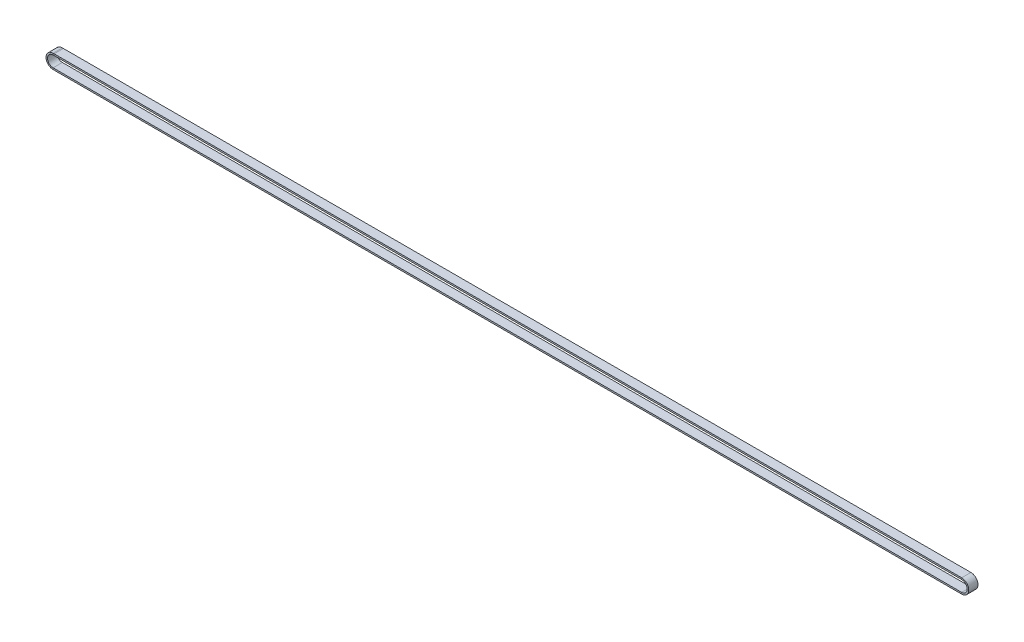
SolidWorks part; units mm, degrees
ref_plane "Front Plane" through (0, 0, 0) normal (0, 0, 1) x (1, 0, 0)
ref_plane "Top Plane" through (0, 0, 0) normal (0, 1, 0) x (1, 0, 0)
ref_plane "Right Plane" through (0, 0, 0) normal (1, 0, 0) x (0, 0, -1)
sketch "Sketch2" plane through (0, 0, -93.7334) normal (0, 0, 1) x (1, 0, 0)
  line L0 (0, 0) -> (1, 0) construction
  line L1 (0, 0) -> (0, 1) construction
  line L2 (-1, 41.3708) -> (883.5206, 41.3708)
  line L3 (883.5206, 27.5708) -> (-1, 27.5708)
  arc A0 (-1, 27.5708) -> (-1, 41.3708) centre (-1, 34.4708) cw
  arc A1 (883.5206, 41.3708) -> (883.5206, 27.5708) centre (883.5206, 34.4708) cw
sketch "Sketch3" plane through (0, 0, 0) normal (1, 0, 0) x (0, 0, -1)
  line L1 (93.7334, 39.8708) -> (84.7334, 39.8708)
  line L2 (93.7334, 39.8708) -> (93.7334, 41.3708)
  line L3 (93.7334, 41.3708) -> (84.7334, 41.3708)
  line L4 (84.7334, 39.8708) -> (84.7334, 41.3708)
  dimension "D1" = 9
  dimension "D2" = 1.5
sweep "Sweep1" add profiles "Sketch3" path "Sketch2"
